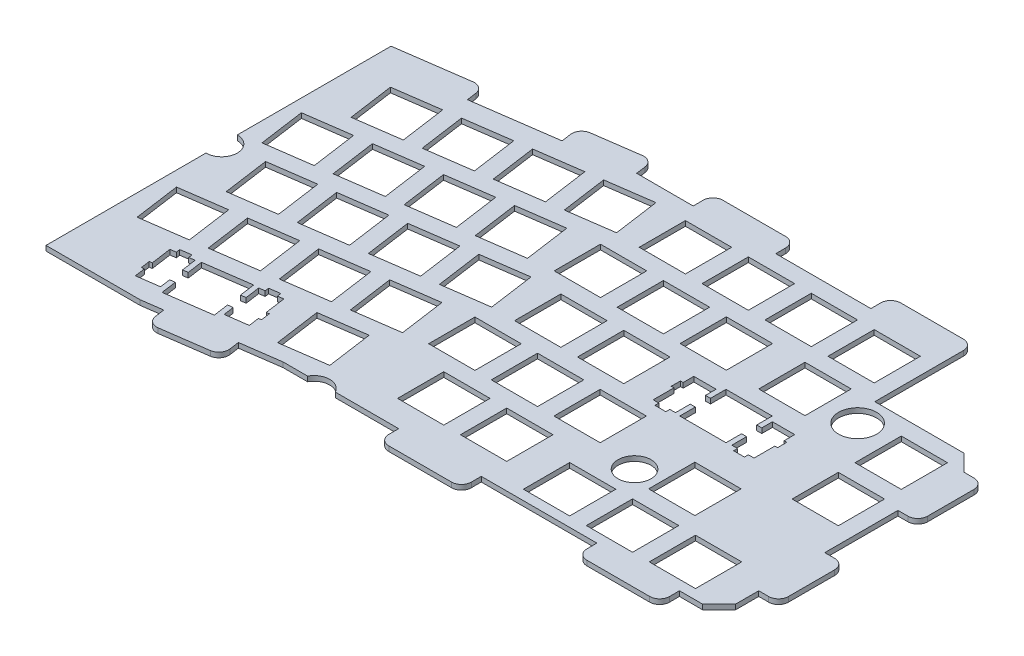
SolidWorks part; units mm, degrees
material "ABS PC"
ref_plane "Front Plane" through (0, 0, 0) normal (0, 0, 1) x (1, 0, 0)
ref_plane "Top Plane" through (0, 0, 0) normal (0, 1, 0) x (1, 0, 0)
ref_plane "Right Plane" through (0, 0, 0) normal (1, 0, 0) x (0, 0, -1)
sketch "Sketch1" plane through (0, 0, 0) normal (0, 1, 0) x (1, 0, 0)
  line L9 (219.1541, 94.4547) -> (218.9175, 96.1382)
  line L10 (165.0257, -13.8474) -> (202.9837, -8.5128)
  line L11 (136.5182, -13.8474) -> (165.0257, -13.8474)
  line L12 (136.5182, 84.5577) -> (136.5182, -13.8474)
  line L13 (218.9175, 96.1382) -> (136.5182, 84.5577)
  line L14 (219.1541, 94.4547) -> (218.9175, 96.1382)
  line L15 (302.957, 70.6408) -> (302.957, 94.4547)
  line L16 (334.9639, 70.6408) -> (302.957, 70.6408)
  line L17 (334.9639, -8.5128) -> (334.9639, 70.6408)
  line L19 (165.0257, -13.8474) -> (202.9837, -8.5128)
  line L20 (136.5182, -13.8474) -> (165.0257, -13.8474)
  line L21 (136.5182, 84.5577) -> (136.5182, -13.8474)
  line L22 (218.9175, 96.1382) -> (136.5182, 84.5577)
  line L24 (302.957, 70.6408) -> (302.957, 94.4547)
  line L25 (334.9639, 70.6408) -> (302.957, 70.6408)
  line L26 (334.9639, -8.5128) -> (334.9639, 70.6408)
  line L172 (302.957, 94.4547) -> (219.1541, 94.4547)
  line L173 (302.957, 94.4547) -> (219.1541, 94.4547)
  line L174 (202.9837, -8.5128) -> (334.9639, -8.5128)
  line L175 (202.9837, -8.5128) -> (334.9639, -8.5128)
  line L263 (136.5182, 95.7385) -> (136.5182, -17.0974) construction
  dimension "D1" = 0
extrude "Boss-Extrude1" add sketch "Sketch1" against normal blind 1.5
sketch "Sketch2" plane through (0, 0, 0) normal (0, 1, 0) x (1, 0, 0)
  line L4 (16.668, 52.1024) -> (2.668, 52.1024)
  line L5 (16.668, 38.1024) -> (16.668, 52.1024)
  line L6 (2.668, 38.1024) -> (16.668, 38.1024)
  line L7 (2.668, 52.1024) -> (2.668, 38.1024)
  line L8 (16.668, 52.1024) -> (2.668, 52.1024)
  line L9 (16.668, 38.1024) -> (16.668, 52.1024)
  line L10 (2.668, 38.1024) -> (16.668, 38.1024)
  line L11 (2.668, 52.1024) -> (2.668, 38.1024)
  line L12 (42.8632, 52.1024) -> (28.8632, 52.1024)
  line L13 (42.8632, 38.1024) -> (42.8632, 52.1024)
  line L14 (28.8632, 38.1024) -> (42.8632, 38.1024)
  line L15 (28.8632, 52.1024) -> (28.8632, 38.1024)
  line L16 (42.8632, 52.1024) -> (28.8632, 52.1024)
  line L17 (42.8632, 38.1024) -> (42.8632, 52.1024)
  line L18 (28.8632, 38.1024) -> (42.8632, 38.1024)
  line L19 (28.8632, 52.1024) -> (28.8632, 38.1024)
  line L20 (241.1855, 51.3524) -> (227.1855, 51.3524)
  line L21 (241.1855, 37.3524) -> (241.1855, 51.3524)
  line L22 (227.1855, 37.3524) -> (241.1855, 37.3524)
  line L23 (227.1855, 51.3524) -> (227.1855, 37.3524)
  line L24 (241.1855, 51.3524) -> (227.1855, 51.3524)
  line L25 (241.1855, 37.3524) -> (241.1855, 51.3524)
  line L26 (227.1855, 37.3524) -> (241.1855, 37.3524)
  line L27 (227.1855, 51.3524) -> (227.1855, 37.3524)
  line L28 (178.1211, 64.9018) -> (180.0695, 51.0381)
  line L29 (180.0695, 51.0381) -> (193.9333, 52.9865)
  line L30 (193.9333, 52.9865) -> (191.9848, 66.8503)
  line L31 (191.9848, 66.8503) -> (178.1211, 64.9018)
  line L32 (178.1211, 64.9018) -> (180.0695, 51.0381)
  line L33 (180.0695, 51.0381) -> (193.9333, 52.9865)
  line L34 (193.9333, 52.9865) -> (191.9848, 66.8503)
  line L35 (191.9848, 66.8503) -> (178.1211, 64.9018)
  line L36 (104.7514, 50.596) -> (118.6152, 48.6476)
  line L37 (118.6152, 48.6476) -> (120.5636, 62.5114)
  line L38 (120.5636, 62.5114) -> (106.6998, 64.4598)
  line L39 (106.6998, 64.4598) -> (104.7514, 50.596)
  line L40 (104.7514, 50.596) -> (118.6152, 48.6476)
  line L41 (118.6152, 48.6476) -> (120.5636, 62.5114)
  line L42 (120.5636, 62.5114) -> (106.6998, 64.4598)
  line L43 (106.6998, 64.4598) -> (104.7514, 50.596)
  line L44 (159.2557, 62.2517) -> (161.2042, 48.388)
  line L45 (161.2042, 48.388) -> (175.0679, 50.3364)
  line L46 (175.0679, 50.3364) -> (173.1195, 64.2001)
  line L47 (173.1195, 64.2001) -> (159.2557, 62.2517)
  line L48 (159.2557, 62.2517) -> (161.2042, 48.388)
  line L49 (161.2042, 48.388) -> (175.0679, 50.3364)
  line L50 (175.0679, 50.3364) -> (173.1195, 64.2001)
  line L51 (173.1195, 64.2001) -> (159.2557, 62.2517)
  line L52 (156.2021, 47.683) -> (154.2536, 61.5467)
  line L53 (154.2536, 61.5467) -> (140.3899, 59.5983)
  line L54 (140.3899, 59.5983) -> (142.3383, 45.7346)
  line L55 (142.3383, 45.7346) -> (156.2021, 47.683)
  line L56 (156.2021, 47.683) -> (154.2536, 61.5467)
  line L57 (154.2536, 61.5467) -> (140.3899, 59.5983)
  line L58 (140.3899, 59.5983) -> (142.3383, 45.7346)
  line L59 (142.3383, 45.7346) -> (156.2021, 47.683)
  line L60 (67.0198, 55.899) -> (80.8836, 53.9505)
  line L61 (80.8836, 53.9505) -> (82.832, 67.8143)
  line L62 (82.832, 67.8143) -> (68.9683, 69.7627)
  line L63 (68.9683, 69.7627) -> (67.0198, 55.899)
  line L64 (67.0198, 55.899) -> (80.8836, 53.9505)
  line L65 (80.8836, 53.9505) -> (82.832, 67.8143)
  line L66 (82.832, 67.8143) -> (68.9683, 69.7627)
  line L67 (68.9683, 69.7627) -> (67.0198, 55.899)
  line L68 (196.9864, 67.5526) -> (198.9348, 53.6888)
  line L69 (198.9348, 53.6888) -> (212.7985, 55.6372)
  line L70 (212.7985, 55.6372) -> (210.8501, 69.501)
  line L71 (210.8501, 69.501) -> (196.9864, 67.5526)
  line L72 (196.9864, 67.5526) -> (198.9348, 53.6888)
  line L73 (198.9348, 53.6888) -> (212.7985, 55.6372)
  line L74 (212.7985, 55.6372) -> (210.8501, 69.501)
  line L75 (210.8501, 69.501) -> (196.9864, 67.5526)
  line L76 (329.9639, 65.6408) -> (315.9639, 65.6408)
  line L77 (329.9639, 51.6408) -> (329.9639, 65.6408)
  line L78 (315.9639, 51.6408) -> (329.9639, 51.6408)
  line L79 (315.9639, 65.6408) -> (315.9639, 51.6408)
  line L80 (329.9639, 65.6408) -> (315.9639, 65.6408)
  line L81 (329.9639, 51.6408) -> (329.9639, 65.6408)
  line L82 (315.9639, 51.6408) -> (329.9639, 51.6408)
  line L83 (315.9639, 65.6408) -> (315.9639, 51.6408)
  line L84 (101.698, 65.1623) -> (87.8343, 67.1107)
  line L85 (87.8343, 67.1107) -> (85.8859, 53.247)
  line L86 (85.8859, 53.247) -> (99.7496, 51.2985)
  line L87 (99.7496, 51.2985) -> (101.698, 65.1623)
  line L88 (101.698, 65.1623) -> (87.8343, 67.1107)
  line L89 (87.8343, 67.1107) -> (85.8859, 53.247)
  line L90 (85.8859, 53.247) -> (99.7496, 51.2985)
  line L91 (99.7496, 51.2985) -> (101.698, 65.1623)
  line L92 (253.1873, 70.4036) -> (239.1873, 70.4036)
  line L93 (253.1873, 56.4036) -> (253.1873, 70.4036)
  line L94 (239.1873, 56.4036) -> (253.1873, 56.4036)
  line L95 (239.1873, 70.4036) -> (239.1873, 56.4036)
  line L96 (253.1873, 70.4036) -> (239.1873, 70.4036)
  line L97 (253.1873, 56.4036) -> (253.1873, 70.4036)
  line L98 (239.1873, 56.4036) -> (253.1873, 56.4036)
  line L99 (239.1873, 70.4036) -> (239.1873, 56.4036)
  line L100 (272.2384, 70.4036) -> (258.2384, 70.4036)
  line L101 (272.2384, 56.4036) -> (272.2384, 70.4036)
  line L102 (258.2384, 56.4036) -> (272.2384, 56.4036)
  line L103 (258.2384, 70.4036) -> (258.2384, 56.4036)
  line L104 (272.2384, 70.4036) -> (258.2384, 70.4036)
  line L105 (272.2384, 56.4036) -> (272.2384, 70.4036)
  line L106 (258.2384, 56.4036) -> (272.2384, 56.4036)
  line L107 (258.2384, 70.4036) -> (258.2384, 56.4036)
  line L108 (296.0529, 70.4036) -> (282.0529, 70.4036)
  line L109 (296.0529, 56.4036) -> (296.0529, 70.4036)
  line L110 (282.0529, 56.4036) -> (296.0529, 56.4036)
  line L111 (282.0529, 70.4036) -> (282.0529, 56.4036)
  line L112 (296.0529, 70.4036) -> (282.0529, 70.4036)
  line L113 (296.0529, 56.4036) -> (296.0529, 70.4036)
  line L114 (282.0529, 56.4036) -> (296.0529, 56.4036)
  line L115 (282.0529, 70.4036) -> (282.0529, 56.4036)
  line L116 (63.9638, 70.468) -> (50.1, 72.4164)
  line L117 (50.1, 72.4164) -> (48.1516, 58.5526)
  line L118 (48.1516, 58.5526) -> (62.0153, 56.6042)
  line L119 (62.0153, 56.6042) -> (63.9638, 70.468)
  line L120 (63.9638, 70.468) -> (50.1, 72.4164)
  line L121 (50.1, 72.4164) -> (48.1516, 58.5526)
  line L122 (48.1516, 58.5526) -> (62.0153, 56.6042)
  line L123 (62.0153, 56.6042) -> (63.9638, 70.468)
  line L124 (157.57, -5.1025) -> (158.0197, -8.301)
  line L125 (158.0197, -8.301) -> (164.7049, -7.3597)
  line L126 (164.7049, -7.3597) -> (164.2552, -4.1612)
  line L127 (164.2552, -4.1612) -> (165.7652, -3.9487)
  line L128 (165.7652, -3.9487) -> (166.4193, -8.6024)
  line L129 (166.4193, -8.6024) -> (180.283, -6.654)
  line L130 (180.283, -6.654) -> (179.6288, -1.9986)
  line L131 (179.6288, -1.9986) -> (181.1399, -1.7869)
  line L132 (181.1399, -1.7869) -> (181.5889, -4.9856)
  line L133 (181.5889, -4.9856) -> (188.2726, -4.0495)
  line L134 (188.2726, -4.0495) -> (187.8237, -0.8493)
  line L135 (187.8237, -0.8493) -> (188.6407, -0.7352)
  line L136 (188.6407, -0.7352) -> (188.2539, 2.0361)
  line L137 (188.2539, 2.0361) -> (187.4358, 1.922)
  line L138 (187.4358, 1.922) -> (186.5659, 8.1321)
  line L139 (186.5659, 8.1321) -> (184.8567, 7.8916)
  line L140 (184.8567, 7.8916) -> (184.6901, 9.0809)
  line L141 (184.6901, 9.0809) -> (181.4217, 8.6218)
  line L142 (181.4217, 8.6218) -> (181.5893, 7.4338)
  line L143 (181.5893, 7.4338) -> (179.8801, 7.1932)
  line L144 (179.8801, 7.1932) -> (180.5017, 2.7678)
  line L145 (180.5017, 2.7678) -> (178.9915, 2.5561)
  line L146 (178.9915, 2.5561) -> (178.338, 7.2102)
  line L147 (178.338, 7.2102) -> (164.4743, 5.2618)
  line L148 (164.4743, 5.2618) -> (165.1265, 0.6064)
  line L149 (165.1265, 0.6064) -> (163.6163, 0.3958)
  line L150 (163.6163, 0.3958) -> (162.9951, 4.8211)
  line L151 (162.9951, 4.8211) -> (161.287, 4.5816)
  line L152 (161.287, 4.5816) -> (161.1202, 5.771)
  line L153 (161.1202, 5.771) -> (157.8529, 5.3113)
  line L154 (157.8529, 5.3113) -> (158.0197, 4.1233)
  line L155 (158.0197, 4.1233) -> (156.3089, 3.8836)
  line L156 (156.3089, 3.8836) -> (157.1794, -2.3298)
  line L157 (157.1794, -2.3298) -> (156.3634, -2.4444)
  line L158 (156.3634, -2.4444) -> (156.754, -5.2171)
  line L159 (156.754, -5.2171) -> (157.57, -5.1025)
  line L160 (157.57, -5.1025) -> (158.0197, -8.301)
  line L161 (158.0197, -8.301) -> (164.7049, -7.3597)
  line L162 (164.7049, -7.3597) -> (164.2552, -4.1612)
  line L163 (164.2552, -4.1612) -> (165.7652, -3.9487)
  line L164 (165.7652, -3.9487) -> (166.4193, -8.6024)
  line L165 (166.4193, -8.6024) -> (180.283, -6.654)
  line L166 (180.283, -6.654) -> (179.6288, -1.9986)
  line L167 (179.6288, -1.9986) -> (181.1399, -1.7869)
  line L168 (181.1399, -1.7869) -> (181.5889, -4.9856)
  line L169 (181.5889, -4.9856) -> (188.2726, -4.0495)
  line L170 (188.2726, -4.0495) -> (187.8237, -0.8493)
  line L171 (187.8237, -0.8493) -> (188.6407, -0.7352)
  line L172 (188.6407, -0.7352) -> (188.2539, 2.0361)
  line L173 (188.2539, 2.0361) -> (187.4358, 1.922)
  line L174 (187.4358, 1.922) -> (186.5659, 8.1321)
  line L175 (186.5659, 8.1321) -> (184.8567, 7.8916)
  line L176 (184.8567, 7.8916) -> (184.6901, 9.0809)
  line L177 (184.6901, 9.0809) -> (181.4217, 8.6218)
  line L178 (181.4217, 8.6218) -> (181.5893, 7.4338)
  line L179 (181.5893, 7.4338) -> (179.8801, 7.1932)
  line L180 (179.8801, 7.1932) -> (180.5017, 2.7678)
  line L181 (180.5017, 2.7678) -> (178.9915, 2.5561)
  line L182 (178.9915, 2.5561) -> (178.338, 7.2102)
  line L183 (178.338, 7.2102) -> (164.4743, 5.2618)
  line L184 (164.4743, 5.2618) -> (165.1265, 0.6064)
  line L185 (165.1265, 0.6064) -> (163.6163, 0.3958)
  line L186 (163.6163, 0.3958) -> (162.9951, 4.8211)
  line L187 (162.9951, 4.8211) -> (161.287, 4.5816)
  line L188 (161.287, 4.5816) -> (161.1202, 5.771)
  line L189 (161.1202, 5.771) -> (157.8529, 5.3113)
  line L190 (157.8529, 5.3113) -> (158.0197, 4.1233)
  line L191 (158.0197, 4.1233) -> (156.3089, 3.8836)
  line L192 (156.3089, 3.8836) -> (157.1794, -2.3298)
  line L193 (157.1794, -2.3298) -> (156.3634, -2.4444)
  line L194 (156.3634, -2.4444) -> (156.754, -5.2171)
  line L195 (156.754, -5.2171) -> (157.57, -5.1025)
  line L196 (147.1695, 79.7839) -> (149.118, 65.9202)
  line L197 (149.118, 65.9202) -> (162.9817, 67.8686)
  line L198 (162.9817, 67.8686) -> (161.0333, 81.7324)
  line L199 (161.0333, 81.7324) -> (147.1695, 79.7839)
  line L200 (147.1695, 79.7839) -> (149.118, 65.9202)
  line L201 (149.118, 65.9202) -> (162.9817, 67.8686)
  line L202 (162.9817, 67.8686) -> (161.0333, 81.7324)
  line L203 (161.0333, 81.7324) -> (147.1695, 79.7839)
  line L204 (16.9533, 71.1536) -> (2.9533, 71.1536)
  line L205 (16.9533, 57.1536) -> (16.9533, 71.1536)
  line L206 (2.9533, 57.1536) -> (16.9533, 57.1536)
  line L207 (2.9533, 71.1536) -> (2.9533, 57.1536)
  line L208 (16.9533, 71.1536) -> (2.9533, 71.1536)
  line L209 (16.9533, 57.1536) -> (16.9533, 71.1536)
  line L210 (2.9533, 57.1536) -> (16.9533, 57.1536)
  line L211 (2.9533, 71.1536) -> (2.9533, 57.1536)
  line L212 (40.7687, 71.1536) -> (26.7687, 71.1536)
  line L213 (40.7687, 57.1536) -> (40.7687, 71.1536)
  line L214 (26.7687, 57.1536) -> (40.7687, 57.1536)
  line L215 (26.7687, 71.1536) -> (26.7687, 57.1536)
  line L216 (40.7687, 71.1536) -> (26.7687, 71.1536)
  line L217 (40.7687, 57.1536) -> (40.7687, 71.1536)
  line L218 (26.7687, 57.1536) -> (40.7687, 57.1536)
  line L219 (26.7687, 71.1536) -> (26.7687, 57.1536)
  line L220 (220.1361, 56.4036) -> (234.1361, 56.4036)
  line L221 (220.1361, 70.4036) -> (220.1361, 56.4036)
  line L222 (234.1361, 70.4036) -> (220.1361, 70.4036)
  line L223 (234.1361, 56.4036) -> (234.1361, 70.4036)
  line L224 (220.1361, 56.4036) -> (234.1361, 56.4036)
  line L225 (220.1361, 70.4036) -> (220.1361, 56.4036)
  line L226 (234.1361, 70.4036) -> (220.1361, 70.4036)
  line L227 (234.1361, 56.4036) -> (234.1361, 70.4036)
  line L228 (324.8196, 8.4872) -> (310.8196, 8.4872)
  line L229 (324.8196, -5.5128) -> (324.8196, 8.4872)
  line L230 (310.8196, -5.5128) -> (324.8196, -5.5128)
  line L231 (310.8196, 8.4872) -> (310.8196, -5.5128)
  line L232 (324.8196, 8.4872) -> (310.8196, 8.4872)
  line L233 (324.8196, -5.5128) -> (324.8196, 8.4872)
  line L234 (310.8196, -5.5128) -> (324.8196, -5.5128)
  line L235 (310.8196, 8.4872) -> (310.8196, -5.5128)
  line L236 (184.9019, 85.0909) -> (186.8504, 71.2271)
  line L237 (186.8504, 71.2271) -> (200.7141, 73.1755)
  line L238 (200.7141, 73.1755) -> (198.7657, 87.0393)
  line L239 (198.7657, 87.0393) -> (184.9019, 85.0909)
  line L240 (184.9019, 85.0909) -> (186.8504, 71.2271)
  line L241 (186.8504, 71.2271) -> (200.7141, 73.1755)
  line L242 (200.7141, 73.1755) -> (198.7657, 87.0393)
  line L243 (198.7657, 87.0393) -> (184.9019, 85.0909)
  line L244 (97.9699, 70.7881) -> (111.8336, 68.8397)
  line L245 (111.8336, 68.8397) -> (113.7821, 82.7035)
  line L246 (113.7821, 82.7035) -> (99.9183, 84.6519)
  line L247 (99.9183, 84.6519) -> (97.9699, 70.7881)
  line L248 (97.9699, 70.7881) -> (111.8336, 68.8397)
  line L249 (111.8336, 68.8397) -> (113.7821, 82.7035)
  line L250 (113.7821, 82.7035) -> (99.9183, 84.6519)
  line L251 (99.9183, 84.6519) -> (97.9699, 70.7881)
  line L252 (166.0364, 82.4413) -> (167.9848, 68.5776)
  line L253 (167.9848, 68.5776) -> (181.8485, 70.526)
  line L254 (181.8485, 70.526) -> (179.9001, 84.3897)
  line L255 (179.9001, 84.3897) -> (166.0364, 82.4413)
  line L256 (166.0364, 82.4413) -> (167.9848, 68.5776)
  line L257 (167.9848, 68.5776) -> (181.8485, 70.526)
  line L258 (181.8485, 70.526) -> (179.9001, 84.3897)
  line L259 (179.9001, 84.3897) -> (166.0364, 82.4413)
  line L260 (132.6465, 80.0523) -> (118.7828, 82.0008)
  line L261 (118.7828, 82.0008) -> (116.8343, 68.137)
  line L262 (116.8343, 68.137) -> (130.6981, 66.1886)
  line L263 (130.6981, 66.1886) -> (132.6465, 80.0523)
  line L264 (132.6465, 80.0523) -> (118.7828, 82.0008)
  line L265 (118.7828, 82.0008) -> (116.8343, 68.137)
  line L266 (116.8343, 68.137) -> (130.6981, 66.1886)
  line L267 (130.6981, 66.1886) -> (132.6465, 80.0523)
  line L268 (111.1042, 1.3782) -> (109.5931, 1.5905)
  line L269 (109.5931, 1.5905) -> (110.2481, 6.2457)
  line L270 (110.2481, 6.2457) -> (96.3844, 8.1942)
  line L271 (96.3844, 8.1942) -> (95.7296, 3.5418)
  line L272 (95.7296, 3.5418) -> (94.2205, 3.7527)
  line L273 (94.2205, 3.7527) -> (94.8425, 8.1806)
  line L274 (94.8425, 8.1806) -> (93.1334, 8.4204)
  line L275 (93.1334, 8.4204) -> (93.3014, 9.6083)
  line L276 (93.3014, 9.6083) -> (90.0324, 10.0671)
  line L277 (90.0324, 10.0671) -> (89.8659, 8.8792)
  line L278 (89.8659, 8.8792) -> (88.1583, 9.1189)
  line L279 (88.1583, 9.1189) -> (87.2845, 2.9106)
  line L280 (87.2845, 2.9106) -> (86.4675, 3.0249)
  line L281 (86.4675, 3.0249) -> (86.0773, 0.2521)
  line L282 (86.0773, 0.2521) -> (86.8948, 0.1364)
  line L283 (86.8948, 0.1364) -> (86.4453, -3.0609)
  line L284 (86.4453, -3.0609) -> (93.1306, -4.0007)
  line L285 (93.1306, -4.0007) -> (93.5796, -0.8021)
  line L286 (93.5796, -0.8021) -> (95.0907, -1.0143)
  line L287 (95.0907, -1.0143) -> (94.4357, -5.6696)
  line L288 (94.4357, -5.6696) -> (108.2995, -7.618)
  line L289 (108.2995, -7.618) -> (108.9549, -2.9641)
  line L290 (108.9549, -2.9641) -> (110.465, -3.1765)
  line L291 (110.465, -3.1765) -> (110.0157, -6.3751)
  line L292 (110.0157, -6.3751) -> (116.699, -7.3155)
  line L293 (116.699, -7.3155) -> (117.1503, -4.1155)
  line L294 (117.1503, -4.1155) -> (117.9673, -4.2313)
  line L295 (117.9673, -4.2313) -> (118.3576, -1.4586)
  line L296 (118.3576, -1.4586) -> (117.5405, -1.3441)
  line L297 (117.5405, -1.3441) -> (118.4121, 4.8656)
  line L298 (118.4121, 4.8656) -> (116.7015, 5.1061)
  line L299 (116.7015, 5.1061) -> (116.8685, 6.2954)
  line L300 (116.8685, 6.2954) -> (113.6013, 6.7543)
  line L301 (113.6013, 6.7543) -> (113.4343, 5.5663)
  line L302 (113.4343, 5.5663) -> (111.7252, 5.8061)
  line L303 (111.7252, 5.8061) -> (111.1042, 1.3782)
  line L304 (111.1042, 1.3782) -> (109.5931, 1.5905)
  line L305 (109.5931, 1.5905) -> (110.2481, 6.2457)
  line L306 (110.2481, 6.2457) -> (96.3844, 8.1942)
  line L307 (96.3844, 8.1942) -> (95.7296, 3.5418)
  line L308 (95.7296, 3.5418) -> (94.2205, 3.7527)
  line L309 (94.2205, 3.7527) -> (94.8425, 8.1806)
  line L310 (94.8425, 8.1806) -> (93.1334, 8.4204)
  line L311 (93.1334, 8.4204) -> (93.3014, 9.6083)
  line L312 (93.3014, 9.6083) -> (90.0324, 10.0671)
  line L313 (90.0324, 10.0671) -> (89.8659, 8.8792)
  line L314 (89.8659, 8.8792) -> (88.1583, 9.1189)
  line L315 (88.1583, 9.1189) -> (87.2845, 2.9106)
  line L316 (87.2845, 2.9106) -> (86.4675, 3.0249)
  line L317 (86.4675, 3.0249) -> (86.0773, 0.2521)
  line L318 (86.0773, 0.2521) -> (86.8948, 0.1364)
  line L319 (86.8948, 0.1364) -> (86.4453, -3.0609)
  line L320 (86.4453, -3.0609) -> (93.1306, -4.0007)
  line L321 (93.1306, -4.0007) -> (93.5796, -0.8021)
  line L322 (93.5796, -0.8021) -> (95.0907, -1.0143)
  line L323 (95.0907, -1.0143) -> (94.4357, -5.6696)
  line L324 (94.4357, -5.6696) -> (108.2995, -7.618)
  line L325 (108.2995, -7.618) -> (108.9549, -2.9641)
  line L326 (108.9549, -2.9641) -> (110.465, -3.1765)
  line L327 (110.465, -3.1765) -> (110.0157, -6.3751)
  line L328 (110.0157, -6.3751) -> (116.699, -7.3155)
  line L329 (116.699, -7.3155) -> (117.1503, -4.1155)
  line L330 (117.1503, -4.1155) -> (117.9673, -4.2313)
  line L331 (117.9673, -4.2313) -> (118.3576, -1.4586)
  line L332 (118.3576, -1.4586) -> (117.5405, -1.3441)
  line L333 (117.5405, -1.3441) -> (118.4121, 4.8656)
  line L334 (118.4121, 4.8656) -> (116.7015, 5.1061)
  line L335 (116.7015, 5.1061) -> (116.8685, 6.2954)
  line L336 (116.8685, 6.2954) -> (113.6013, 6.7543)
  line L337 (113.6013, 6.7543) -> (113.4343, 5.5663)
  line L338 (113.4343, 5.5663) -> (111.7252, 5.8061)
  line L339 (111.7252, 5.8061) -> (111.1042, 1.3782)
  line L340 (56.7058, -0.3668) -> (70.5695, -2.3152)
  line L341 (70.5695, -2.3152) -> (72.518, 11.5486)
  line L342 (72.518, 11.5486) -> (58.6542, 13.497)
  line L343 (58.6542, 13.497) -> (56.7058, -0.3668)
  line L344 (56.7058, -0.3668) -> (70.5695, -2.3152)
  line L345 (70.5695, -2.3152) -> (72.518, 11.5486)
  line L346 (72.518, 11.5486) -> (58.6542, 13.497)
  line L347 (58.6542, 13.497) -> (56.7058, -0.3668)
  line L348 (195.1301, 9.5671) -> (197.0785, -4.2966)
  line L349 (197.0785, -4.2966) -> (210.9422, -2.3482)
  line L350 (210.9422, -2.3482) -> (208.9938, 11.5155)
  line L351 (208.9938, 11.5155) -> (195.1301, 9.5671)
  line L352 (195.1301, 9.5671) -> (197.0785, -4.2966)
  line L353 (197.0785, -4.2966) -> (210.9422, -2.3482)
  line L354 (210.9422, -2.3482) -> (208.9938, 11.5155)
  line L355 (208.9938, 11.5155) -> (195.1301, 9.5671)
  line L356 (286.7173, 8.4872) -> (272.7173, 8.4872)
  line L357 (286.7173, -5.5128) -> (286.7173, 8.4872)
  line L358 (272.7173, -5.5128) -> (286.7173, -5.5128)
  line L359 (272.7173, 8.4872) -> (272.7173, -5.5128)
  line L360 (286.7173, 8.4872) -> (272.7173, 8.4872)
  line L361 (286.7173, -5.5128) -> (286.7173, 8.4872)
  line L362 (272.7173, -5.5128) -> (286.7173, -5.5128)
  line L363 (272.7173, 8.4872) -> (272.7173, -5.5128)
  line L364 (291.7685, -5.5128) -> (305.7685, -5.5128)
  line L365 (291.7685, 8.4872) -> (291.7685, -5.5128)
  line L366 (305.7685, 8.4872) -> (291.7685, 8.4872)
  line L367 (305.7685, -5.5128) -> (305.7685, 8.4872)
  line L368 (291.7685, -5.5128) -> (305.7685, -5.5128)
  line L369 (291.7685, 8.4872) -> (291.7685, -5.5128)
  line L370 (305.7685, 8.4872) -> (291.7685, 8.4872)
  line L371 (305.7685, -5.5128) -> (305.7685, 8.4872)
  line L372 (329.9639, 89.4547) -> (315.9639, 89.4547)
  line L373 (329.9639, 75.4547) -> (329.9639, 89.4547)
  line L374 (315.9639, 75.4547) -> (329.9639, 75.4547)
  line L375 (315.9639, 89.4547) -> (315.9639, 75.4547)
  line L376 (329.9639, 89.4547) -> (315.9639, 89.4547)
  line L377 (329.9639, 75.4547) -> (329.9639, 89.4547)
  line L378 (315.9639, 75.4547) -> (329.9639, 75.4547)
  line L379 (315.9639, 89.4547) -> (315.9639, 75.4547)
  line L380 (60.2383, 76.0914) -> (74.102, 74.143)
  line L381 (74.102, 74.143) -> (76.0505, 88.0067)
  line L382 (76.0505, 88.0067) -> (62.1867, 89.9552)
  line L383 (62.1867, 89.9552) -> (60.2383, 76.0914)
  line L384 (60.2383, 76.0914) -> (74.102, 74.143)
  line L385 (74.102, 74.143) -> (76.0505, 88.0067)
  line L386 (76.0505, 88.0067) -> (62.1867, 89.9552)
  line L387 (62.1867, 89.9552) -> (60.2383, 76.0914)
  line L388 (203.7677, 87.7438) -> (205.7162, 73.88)
  line L389 (205.7162, 73.88) -> (219.5799, 75.8285)
  line L390 (219.5799, 75.8285) -> (217.6315, 89.6922)
  line L391 (217.6315, 89.6922) -> (203.7677, 87.7438)
  line L392 (203.7677, 87.7438) -> (205.7162, 73.88)
  line L393 (205.7162, 73.88) -> (219.5799, 75.8285)
  line L394 (219.5799, 75.8285) -> (217.6315, 89.6922)
  line L395 (217.6315, 89.6922) -> (203.7677, 87.7438)
  line L396 (94.9166, 85.3549) -> (81.0528, 87.3033)
  line L397 (81.0528, 87.3033) -> (79.1044, 73.4396)
  line L398 (79.1044, 73.4396) -> (92.9682, 71.4911)
  line L399 (92.9682, 71.4911) -> (94.9166, 85.3549)
  line L400 (94.9166, 85.3549) -> (81.0528, 87.3033)
  line L401 (81.0528, 87.3033) -> (79.1044, 73.4396)
  line L402 (79.1044, 73.4396) -> (92.9682, 71.4911)
  line L403 (92.9682, 71.4911) -> (94.9166, 85.3549)
  line L404 (13.9985, 14.0032) -> (-0.0015, 14.0032)
  line L405 (13.9985, 0.0032) -> (13.9985, 14.0032)
  line L406 (-0.0015, 0.0032) -> (13.9985, 0.0032)
  line L407 (-0.0015, 14.0032) -> (-0.0015, 0.0032)
  line L408 (13.9985, 14.0032) -> (-0.0015, 14.0032)
  line L409 (13.9985, 0.0032) -> (13.9985, 14.0032)
  line L410 (-0.0015, 0.0032) -> (13.9985, 0.0032)
  line L411 (-0.0015, 14.0032) -> (-0.0015, 0.0032)
  line L412 (37.8153, 14) -> (23.8153, 14)
  line L413 (37.8153, 0) -> (37.8153, 14)
  line L414 (23.8153, 0) -> (37.8153, 0)
  line L415 (23.8153, 14) -> (23.8153, 0)
  line L416 (37.8153, 14) -> (23.8153, 14)
  line L417 (37.8153, 0) -> (37.8153, 14)
  line L418 (23.8153, 0) -> (37.8153, 0)
  line L419 (23.8153, 14) -> (23.8153, 0)
  line L420 (243.8527, 13.25) -> (229.8527, 13.25)
  line L421 (243.8527, -0.75) -> (243.8527, 13.25)
  line L422 (229.8527, -0.75) -> (243.8527, -0.75)
  line L423 (229.8527, 13.25) -> (229.8527, -0.75)
  line L424 (243.8527, 13.25) -> (229.8527, 13.25)
  line L425 (243.8527, -0.75) -> (243.8527, 13.25)
  line L426 (229.8527, -0.75) -> (243.8527, -0.75)
  line L427 (229.8527, 13.25) -> (229.8527, -0.75)
  line L428 (248.9019, -0.75) -> (262.9019, -0.75)
  line L429 (248.9019, 13.25) -> (248.9019, -0.75)
  line L430 (262.9019, 13.25) -> (248.9019, 13.25)
  line L431 (262.9019, -0.75) -> (262.9019, 13.25)
  line L432 (248.9019, -0.75) -> (262.9019, -0.75)
  line L433 (248.9019, 13.25) -> (248.9019, -0.75)
  line L434 (262.9019, 13.25) -> (248.9019, 13.25)
  line L435 (262.9019, -0.75) -> (262.9019, 13.25)
  line L436 (240.8054, 89.4547) -> (226.8054, 89.4547)
  line L437 (240.8054, 75.4547) -> (240.8054, 89.4547)
  line L438 (226.8054, 75.4547) -> (240.8054, 75.4547)
  line L439 (226.8054, 89.4547) -> (226.8054, 75.4547)
  line L440 (240.8054, 89.4547) -> (226.8054, 89.4547)
  line L441 (240.8054, 75.4547) -> (240.8054, 89.4547)
  line L442 (226.8054, 75.4547) -> (240.8054, 75.4547)
  line L443 (226.8054, 89.4547) -> (226.8054, 75.4547)
  line L444 (259.8537, 89.4547) -> (245.8537, 89.4547)
  line L445 (259.8537, 75.4547) -> (259.8537, 89.4547)
  line L446 (245.8537, 75.4547) -> (259.8537, 75.4547)
  line L447 (245.8537, 89.4547) -> (245.8537, 75.4547)
  line L448 (259.8537, 89.4547) -> (245.8537, 89.4547)
  line L449 (259.8537, 75.4547) -> (259.8537, 89.4547)
  line L450 (245.8537, 75.4547) -> (259.8537, 75.4547)
  line L451 (245.8537, 89.4547) -> (245.8537, 75.4547)
  line L452 (278.9058, 89.4547) -> (264.9058, 89.4547)
  line L453 (278.9058, 75.4547) -> (278.9058, 89.4547)
  line L454 (264.9058, 75.4547) -> (278.9058, 75.4547)
  line L455 (264.9058, 89.4547) -> (264.9058, 75.4547)
  line L456 (278.9058, 89.4547) -> (264.9058, 89.4547)
  line L457 (278.9058, 75.4547) -> (278.9058, 89.4547)
  line L458 (264.9058, 75.4547) -> (278.9058, 75.4547)
  line L459 (264.9058, 89.4547) -> (264.9058, 75.4547)
  line L460 (283.957, 75.4547) -> (297.957, 75.4547)
  line L461 (283.957, 89.4547) -> (283.957, 75.4547)
  line L462 (297.957, 89.4547) -> (283.957, 89.4547)
  line L463 (297.957, 75.4547) -> (297.957, 89.4547)
  line L464 (283.957, 75.4547) -> (297.957, 75.4547)
  line L465 (283.957, 89.4547) -> (283.957, 75.4547)
  line L466 (297.957, 89.4547) -> (283.957, 89.4547)
  line L467 (297.957, 75.4547) -> (297.957, 89.4547)
  line L468 (94.7285, 13.5308) -> (108.5923, 11.5823)
  line L469 (108.5923, 11.5823) -> (110.5407, 25.4461)
  line L470 (110.5407, 25.4461) -> (96.6769, 27.3945)
  line L471 (96.6769, 27.3945) -> (94.7285, 13.5308)
  line L472 (94.7285, 13.5308) -> (108.5923, 11.5823)
  line L473 (108.5923, 11.5823) -> (110.5407, 25.4461)
  line L474 (110.5407, 25.4461) -> (96.6769, 27.3945)
  line L475 (96.6769, 27.3945) -> (94.7285, 13.5308)
  line L476 (159.8401, 23.8549) -> (161.7885, 9.9912)
  line L477 (161.7885, 9.9912) -> (175.6523, 11.9396)
  line L478 (175.6523, 11.9396) -> (173.7039, 25.8034)
  line L479 (173.7039, 25.8034) -> (159.8401, 23.8549)
  line L480 (159.8401, 23.8549) -> (161.7885, 9.9912)
  line L481 (161.7885, 9.9912) -> (175.6523, 11.9396)
  line L482 (175.6523, 11.9396) -> (173.7039, 25.8034)
  line L483 (173.7039, 25.8034) -> (159.8401, 23.8549)
  line L484 (113.5965, 10.8786) -> (127.4602, 8.9301)
  line L485 (127.4602, 8.9301) -> (129.4086, 22.7939)
  line L486 (129.4086, 22.7939) -> (115.5449, 24.7423)
  line L487 (115.5449, 24.7423) -> (113.5965, 10.8786)
  line L488 (113.5965, 10.8786) -> (127.4602, 8.9301)
  line L489 (127.4602, 8.9301) -> (129.4086, 22.7939)
  line L490 (129.4086, 22.7939) -> (115.5449, 24.7423)
  line L491 (115.5449, 24.7423) -> (113.5965, 10.8786)
  line L492 (156.7871, 9.2881) -> (154.8387, 23.1518)
  line L493 (154.8387, 23.1518) -> (140.975, 21.2034)
  line L494 (140.975, 21.2034) -> (142.9234, 7.3397)
  line L495 (142.9234, 7.3397) -> (156.7871, 9.2881)
  line L496 (156.7871, 9.2881) -> (154.8387, 23.1518)
  line L497 (154.8387, 23.1518) -> (140.975, 21.2034)
  line L498 (140.975, 21.2034) -> (142.9234, 7.3397)
  line L499 (142.9234, 7.3397) -> (156.7871, 9.2881)
  line L500 (41.37, 78.7439) -> (55.2337, 76.7955)
  line L501 (55.2337, 76.7955) -> (57.1821, 90.6593)
  line L502 (57.1821, 90.6593) -> (43.3184, 92.6077)
  line L503 (43.3184, 92.6077) -> (41.37, 78.7439)
  line L504 (41.37, 78.7439) -> (55.2337, 76.7955)
  line L505 (55.2337, 76.7955) -> (57.1821, 90.6593)
  line L506 (57.1821, 90.6593) -> (43.3184, 92.6077)
  line L507 (43.3184, 92.6077) -> (41.37, 78.7439)
  line L508 (14.667, 90.2051) -> (0.667, 90.2051)
  line L509 (14.667, 76.2051) -> (14.667, 90.2051)
  line L510 (0.667, 76.2051) -> (14.667, 76.2051)
  line L511 (0.667, 90.2051) -> (0.667, 76.2051)
  line L512 (14.667, 90.2051) -> (0.667, 90.2051)
  line L513 (14.667, 76.2051) -> (14.667, 90.2051)
  line L514 (0.667, 76.2051) -> (14.667, 76.2051)
  line L515 (0.667, 90.2051) -> (0.667, 76.2051)
  line L516 (19.7182, 76.2047) -> (33.7182, 76.2047)
  line L517 (19.7182, 90.2047) -> (19.7182, 76.2047)
  line L518 (33.7182, 90.2047) -> (19.7182, 90.2047)
  line L519 (33.7182, 76.2047) -> (33.7182, 90.2047)
  line L520 (19.7182, 76.2047) -> (33.7182, 76.2047)
  line L521 (19.7182, 90.2047) -> (19.7182, 76.2047)
  line L522 (33.7182, 90.2047) -> (19.7182, 90.2047)
  line L523 (33.7182, 76.2047) -> (33.7182, 90.2047)
  line L524 (197.5716, 29.1561) -> (199.5201, 15.2924)
  line L525 (199.5201, 15.2924) -> (213.3838, 17.2408)
  line L526 (213.3838, 17.2408) -> (211.4354, 31.1046)
  line L527 (211.4354, 31.1046) -> (197.5716, 29.1561)
  line L528 (197.5716, 29.1561) -> (199.5201, 15.2924)
  line L529 (199.5201, 15.2924) -> (213.3838, 17.2408)
  line L530 (213.3838, 17.2408) -> (211.4354, 31.1046)
  line L531 (211.4354, 31.1046) -> (197.5716, 29.1561)
  line L532 (305.5785, 27.5384) -> (291.5785, 27.5384)
  line L533 (305.5785, 13.5384) -> (305.5785, 27.5384)
  line L534 (291.5785, 13.5384) -> (305.5785, 13.5384)
  line L535 (291.5785, 27.5384) -> (291.5785, 13.5384)
  line L536 (305.5785, 27.5384) -> (291.5785, 27.5384)
  line L537 (305.5785, 13.5384) -> (305.5785, 27.5384)
  line L538 (291.5785, 13.5384) -> (305.5785, 13.5384)
  line L539 (291.5785, 27.5384) -> (291.5785, 13.5384)
  line L540 (75.865, 16.1803) -> (89.7287, 14.2318)
  line L541 (89.7287, 14.2318) -> (91.6772, 28.0956)
  line L542 (91.6772, 28.0956) -> (77.8134, 30.044)
  line L543 (77.8134, 30.044) -> (75.865, 16.1803)
  line L544 (75.865, 16.1803) -> (89.7287, 14.2318)
  line L545 (89.7287, 14.2318) -> (91.6772, 28.0956)
  line L546 (91.6772, 28.0956) -> (77.8134, 30.044)
  line L547 (77.8134, 30.044) -> (75.865, 16.1803)
  line L548 (194.5187, 14.5909) -> (192.5702, 28.4546)
  line L549 (192.5702, 28.4546) -> (178.7065, 26.5062)
  line L550 (178.7065, 26.5062) -> (180.6549, 12.6425)
  line L551 (180.6549, 12.6425) -> (194.5187, 14.5909)
  line L552 (194.5187, 14.5909) -> (192.5702, 28.4546)
  line L553 (192.5702, 28.4546) -> (178.7065, 26.5062)
  line L554 (178.7065, 26.5062) -> (180.6549, 12.6425)
  line L555 (180.6549, 12.6425) -> (194.5187, 14.5909)
  line L556 (72.814, 30.7438) -> (58.9503, 32.6922)
  line L557 (58.9503, 32.6922) -> (57.0019, 18.8284)
  line L558 (57.0019, 18.8284) -> (70.8656, 16.88)
  line L559 (70.8656, 16.88) -> (72.814, 30.7438)
  line L560 (72.814, 30.7438) -> (58.9503, 32.6922)
  line L561 (58.9503, 32.6922) -> (57.0019, 18.8284)
  line L562 (57.0019, 18.8284) -> (70.8656, 16.88)
  line L563 (70.8656, 16.88) -> (72.814, 30.7438)
  line L564 (253.1873, 32.3012) -> (239.1873, 32.3012)
  line L565 (253.1873, 18.3012) -> (253.1873, 32.3012)
  line L566 (239.1873, 18.3012) -> (253.1873, 18.3012)
  line L567 (239.1873, 32.3012) -> (239.1873, 18.3012)
  line L568 (253.1873, 32.3012) -> (239.1873, 32.3012)
  line L569 (253.1873, 18.3012) -> (253.1873, 32.3012)
  line L570 (239.1873, 18.3012) -> (253.1873, 18.3012)
  line L571 (239.1873, 32.3012) -> (239.1873, 18.3012)
  line L572 (277.0017, 32.3012) -> (263.0017, 32.3012)
  line L573 (277.0017, 18.3012) -> (277.0017, 32.3012)
  line L574 (263.0017, 18.3012) -> (277.0017, 18.3012)
  line L575 (263.0017, 32.3012) -> (263.0017, 18.3012)
  line L576 (277.0017, 32.3012) -> (263.0017, 32.3012)
  line L577 (277.0017, 18.3012) -> (277.0017, 32.3012)
  line L578 (263.0017, 18.3012) -> (277.0017, 18.3012)
  line L579 (263.0017, 32.3012) -> (263.0017, 18.3012)
  line L580 (106.8174, 31.0676) -> (120.6811, 29.1192)
  line L581 (120.6811, 29.1192) -> (122.6296, 42.9829)
  line L582 (122.6296, 42.9829) -> (108.7658, 44.9313)
  line L583 (108.7658, 44.9313) -> (106.8174, 31.0676)
  line L584 (106.8174, 31.0676) -> (120.6811, 29.1192)
  line L585 (120.6811, 29.1192) -> (122.6296, 42.9829)
  line L586 (122.6296, 42.9829) -> (108.7658, 44.9313)
  line L587 (108.7658, 44.9313) -> (106.8174, 31.0676)
  line L588 (147.7571, 41.3964) -> (149.7055, 27.5327)
  line L589 (149.7055, 27.5327) -> (163.5692, 29.4811)
  line L590 (163.5692, 29.4811) -> (161.6208, 43.3449)
  line L591 (161.6208, 43.3449) -> (147.7571, 41.3964)
  line L592 (147.7571, 41.3964) -> (149.7055, 27.5327)
  line L593 (149.7055, 27.5327) -> (163.5692, 29.4811)
  line L594 (163.5692, 29.4811) -> (161.6208, 43.3449)
  line L595 (161.6208, 43.3449) -> (147.7571, 41.3964)
  line L596 (49.7223, 33.0512) -> (35.7223, 33.0512)
  line L597 (49.7223, 19.0512) -> (49.7223, 33.0512)
  line L598 (35.7223, 19.0512) -> (49.7223, 19.0512)
  line L599 (35.7223, 33.0512) -> (35.7223, 19.0512)
  line L600 (49.7223, 33.0512) -> (35.7223, 33.0512)
  line L601 (49.7223, 19.0512) -> (49.7223, 33.0512)
  line L602 (35.7223, 19.0512) -> (49.7223, 19.0512)
  line L603 (35.7223, 33.0512) -> (35.7223, 19.0512)
  line L604 (220.2319, 18.3012) -> (234.2319, 18.3012)
  line L605 (220.2319, 32.3012) -> (220.2319, 18.3012)
  line L606 (234.2319, 32.3012) -> (220.2319, 32.3012)
  line L607 (234.2319, 18.3012) -> (234.2319, 32.3012)
  line L608 (220.2319, 18.3012) -> (234.2319, 18.3012)
  line L609 (220.2319, 32.3012) -> (220.2319, 18.3012)
  line L610 (234.2319, 32.3012) -> (220.2319, 32.3012)
  line L611 (234.2319, 18.3012) -> (234.2319, 32.3012)
  line L612 (29.4211, 28.3519) -> (29.4211, 31.5821)
  line L613 (29.4211, 31.5821) -> (22.6712, 31.5821)
  line L614 (22.6712, 31.5821) -> (22.6712, 28.3519)
  line L615 (22.6712, 28.3519) -> (21.1456, 28.3519)
  line L616 (21.1456, 28.3519) -> (21.1456, 33.0512)
  line L617 (21.1456, 33.0512) -> (7.1456, 33.0512)
  line L618 (7.1456, 33.0512) -> (7.1456, 28.3521)
  line L619 (7.1456, 28.3521) -> (5.62, 28.3521)
  line L620 (5.62, 28.3521) -> (5.62, 31.5823)
  line L621 (5.62, 31.5823) -> (-1.13, 31.5823)
  line L622 (-1.13, 31.5823) -> (-1.13, 28.3521)
  line L623 (-1.13, 28.3521) -> (-1.9556, 28.3521)
  line L624 (-1.9556, 28.3521) -> (-1.9556, 25.552)
  line L625 (-1.9556, 25.552) -> (-1.13, 25.552)
  line L626 (-1.13, 25.552) -> (-1.13, 19.2814)
  line L627 (-1.13, 19.2814) -> (0.594, 19.2814)
  line L628 (0.594, 19.2814) -> (0.594, 18.081)
  line L629 (0.594, 18.081) -> (3.8945, 18.081)
  line L630 (3.8945, 18.081) -> (3.8945, 19.2814)
  line L631 (3.8945, 19.2814) -> (5.62, 19.2814)
  line L632 (5.62, 19.2814) -> (5.62, 23.7519)
  line L633 (5.62, 23.7519) -> (7.1456, 23.7519)
  line L634 (7.1456, 23.7519) -> (7.1456, 19.0512)
  line L635 (7.1456, 19.0512) -> (21.1456, 19.0512)
  line L636 (21.1456, 19.0512) -> (21.1456, 23.7519)
  line L637 (21.1456, 23.7519) -> (22.6712, 23.7519)
  line L638 (22.6712, 23.7519) -> (22.6712, 19.2814)
  line L639 (22.6712, 19.2814) -> (24.3952, 19.2814)
  line L640 (24.3952, 19.2814) -> (24.3952, 18.081)
  line L641 (24.3952, 18.081) -> (27.6959, 18.081)
  line L642 (27.6959, 18.081) -> (27.6959, 19.2814)
  line L643 (27.6959, 19.2814) -> (29.4211, 19.2814)
  line L644 (29.4211, 19.2814) -> (29.4211, 25.552)
  line L645 (29.4211, 25.552) -> (30.2453, 25.552)
  line L646 (30.2453, 25.552) -> (30.2453, 28.3519)
  line L647 (30.2453, 28.3519) -> (29.4211, 28.3519)
  line L648 (29.4211, 28.3519) -> (29.4211, 31.5821)
  line L649 (29.4211, 31.5821) -> (22.6712, 31.5821)
  line L650 (22.6712, 31.5821) -> (22.6712, 28.3519)
  line L651 (22.6712, 28.3519) -> (21.1456, 28.3519)
  line L652 (21.1456, 28.3519) -> (21.1456, 33.0512)
  line L653 (21.1456, 33.0512) -> (7.1456, 33.0512)
  line L654 (7.1456, 33.0512) -> (7.1456, 28.3521)
  line L655 (7.1456, 28.3521) -> (5.62, 28.3521)
  line L656 (5.62, 28.3521) -> (5.62, 31.5823)
  line L657 (5.62, 31.5823) -> (-1.13, 31.5823)
  line L658 (-1.13, 31.5823) -> (-1.13, 28.3521)
  line L659 (-1.13, 28.3521) -> (-1.9556, 28.3521)
  line L660 (-1.9556, 28.3521) -> (-1.9556, 25.552)
  line L661 (-1.9556, 25.552) -> (-1.13, 25.552)
  line L662 (-1.13, 25.552) -> (-1.13, 19.2814)
  line L663 (-1.13, 19.2814) -> (0.594, 19.2814)
  line L664 (0.594, 19.2814) -> (0.594, 18.081)
  line L665 (0.594, 18.081) -> (3.8945, 18.081)
  line L666 (3.8945, 18.081) -> (3.8945, 19.2814)
  line L667 (3.8945, 19.2814) -> (5.62, 19.2814)
  line L668 (5.62, 19.2814) -> (5.62, 23.7519)
  line L669 (5.62, 23.7519) -> (7.1456, 23.7519)
  line L670 (7.1456, 23.7519) -> (7.1456, 19.0512)
  line L671 (7.1456, 19.0512) -> (21.1456, 19.0512)
  line L672 (21.1456, 19.0512) -> (21.1456, 23.7519)
  line L673 (21.1456, 23.7519) -> (22.6712, 23.7519)
  line L674 (22.6712, 23.7519) -> (22.6712, 19.2814)
  line L675 (22.6712, 19.2814) -> (24.3952, 19.2814)
  line L676 (24.3952, 19.2814) -> (24.3952, 18.081)
  line L677 (24.3952, 18.081) -> (27.6959, 18.081)
  line L678 (27.6959, 18.081) -> (27.6959, 19.2814)
  line L679 (27.6959, 19.2814) -> (29.4211, 19.2814)
  line L680 (29.4211, 19.2814) -> (29.4211, 25.552)
  line L681 (29.4211, 25.552) -> (30.2453, 25.552)
  line L682 (30.2453, 25.552) -> (30.2453, 28.3519)
  line L683 (30.2453, 28.3519) -> (29.4211, 28.3519)
  line L684 (329.9639, 46.5896) -> (315.9639, 46.5896)
  line L685 (329.9639, 32.5896) -> (329.9639, 46.5896)
  line L686 (315.9639, 32.5896) -> (329.9639, 32.5896)
  line L687 (315.9639, 46.5896) -> (315.9639, 32.5896)
  line L688 (329.9639, 46.5896) -> (315.9639, 46.5896)
  line L689 (329.9639, 32.5896) -> (329.9639, 46.5896)
  line L690 (315.9639, 32.5896) -> (329.9639, 32.5896)
  line L691 (315.9639, 46.5896) -> (315.9639, 32.5896)
  line L692 (185.4888, 46.6978) -> (187.4372, 32.834)
  line L693 (187.4372, 32.834) -> (201.301, 34.7824)
  line L694 (201.301, 34.7824) -> (199.3525, 48.6462)
  line L695 (199.3525, 48.6462) -> (185.4888, 46.6978)
  line L696 (185.4888, 46.6978) -> (187.4372, 32.834)
  line L697 (187.4372, 32.834) -> (201.301, 34.7824)
  line L698 (201.301, 34.7824) -> (199.3525, 48.6462)
  line L699 (199.3525, 48.6462) -> (185.4888, 46.6978)
  line L700 (87.9507, 33.7182) -> (101.8145, 31.7697)
  line L701 (101.8145, 31.7697) -> (103.7629, 45.6335)
  line L702 (103.7629, 45.6335) -> (89.8992, 47.5819)
  line L703 (89.8992, 47.5819) -> (87.9507, 33.7182)
  line L704 (87.9507, 33.7182) -> (101.8145, 31.7697)
  line L705 (101.8145, 31.7697) -> (103.7629, 45.6335)
  line L706 (103.7629, 45.6335) -> (89.8992, 47.5819)
  line L707 (89.8992, 47.5819) -> (87.9507, 33.7182)
  line L708 (182.4352, 32.1339) -> (180.4868, 45.9976)
  line L709 (180.4868, 45.9976) -> (166.6231, 44.0492)
  line L710 (166.6231, 44.0492) -> (168.5715, 30.1855)
  line L711 (168.5715, 30.1855) -> (182.4352, 32.1339)
  line L712 (182.4352, 32.1339) -> (180.4868, 45.9976)
  line L713 (180.4868, 45.9976) -> (166.6231, 44.0492)
  line L714 (166.6231, 44.0492) -> (168.5715, 30.1855)
  line L715 (168.5715, 30.1855) -> (182.4352, 32.1339)
  line L716 (50.2174, 39.0227) -> (64.0811, 37.0743)
  line L717 (64.0811, 37.0743) -> (66.0296, 50.938)
  line L718 (66.0296, 50.938) -> (52.1658, 52.8864)
  line L719 (52.1658, 52.8864) -> (50.2174, 39.0227)
  line L720 (50.2174, 39.0227) -> (64.0811, 37.0743)
  line L721 (64.0811, 37.0743) -> (66.0296, 50.938)
  line L722 (66.0296, 50.938) -> (52.1658, 52.8864)
  line L723 (52.1658, 52.8864) -> (50.2174, 39.0227)
  line L724 (204.354, 49.3477) -> (206.3024, 35.4839)
  line L725 (206.3024, 35.4839) -> (220.1662, 37.4324)
  line L726 (220.1662, 37.4324) -> (218.2177, 51.2961)
  line L727 (218.2177, 51.2961) -> (204.354, 49.3477)
  line L728 (204.354, 49.3477) -> (206.3024, 35.4839)
  line L729 (206.3024, 35.4839) -> (220.1662, 37.4324)
  line L730 (220.1662, 37.4324) -> (218.2177, 51.2961)
  line L731 (218.2177, 51.2961) -> (204.354, 49.3477)
  line L732 (84.8976, 48.285) -> (71.0338, 50.2334)
  line L733 (71.0338, 50.2334) -> (69.0854, 36.3697)
  line L734 (69.0854, 36.3697) -> (82.9492, 34.4212)
  line L735 (82.9492, 34.4212) -> (84.8976, 48.285)
  line L736 (84.8976, 48.285) -> (71.0338, 50.2334)
  line L737 (71.0338, 50.2334) -> (69.0854, 36.3697)
  line L738 (69.0854, 36.3697) -> (82.9492, 34.4212)
  line L739 (82.9492, 34.4212) -> (84.8976, 48.285)
  line L740 (260.2367, 51.3524) -> (246.2367, 51.3524)
  line L741 (260.2367, 37.3524) -> (260.2367, 51.3524)
  line L742 (246.2367, 37.3524) -> (260.2367, 37.3524)
  line L743 (246.2367, 51.3524) -> (246.2367, 37.3524)
  line L744 (260.2367, 51.3524) -> (246.2367, 51.3524)
  line L745 (260.2367, 37.3524) -> (260.2367, 51.3524)
  line L746 (246.2367, 37.3524) -> (260.2367, 37.3524)
  line L747 (246.2367, 51.3524) -> (246.2367, 37.3524)
  line L780 (294.4438, 37.5824) -> (294.4438, 36.3823)
  line L781 (294.4438, 36.3823) -> (297.744, 36.3823)
  line L782 (297.744, 36.3823) -> (297.744, 37.5824)
  line L783 (297.744, 37.5824) -> (299.4701, 37.5824)
  line L784 (299.4701, 37.5824) -> (299.4701, 43.8531)
  line L785 (299.4701, 43.8531) -> (300.2941, 43.8531)
  line L786 (300.2941, 43.8531) -> (300.2941, 46.6531)
  line L787 (300.2941, 46.6531) -> (299.4701, 46.6531)
  line L788 (299.4701, 46.6531) -> (299.4701, 49.8833)
  line L789 (299.4701, 49.8833) -> (292.7197, 49.8833)
  line L790 (292.7197, 49.8833) -> (292.7197, 46.6531)
  line L791 (292.7197, 46.6531) -> (291.1946, 46.6531)
  line L792 (291.1946, 46.6531) -> (291.1946, 51.3524)
  line L793 (291.1946, 51.3524) -> (277.1946, 51.3524)
  line L794 (277.1946, 51.3524) -> (277.1946, 46.6533)
  line L795 (277.1946, 46.6533) -> (275.6695, 46.6533)
  line L796 (275.6695, 46.6533) -> (275.6695, 49.8835)
  line L797 (275.6695, 49.8835) -> (268.9191, 49.8835)
  line L798 (268.9191, 49.8835) -> (268.9191, 46.6533)
  line L799 (268.9191, 46.6533) -> (268.094, 46.6533)
  line L800 (268.094, 46.6533) -> (268.094, 43.8531)
  line L801 (268.094, 43.8531) -> (268.9191, 43.8531)
  line L802 (268.9191, 43.8531) -> (268.9191, 37.5824)
  line L803 (268.9191, 37.5824) -> (270.6432, 37.5824)
  line L804 (270.6432, 37.5824) -> (270.6432, 36.3823)
  line L805 (270.6432, 36.3823) -> (273.9434, 36.3823)
  line L806 (273.9434, 36.3823) -> (273.9434, 37.5824)
  line L807 (273.9434, 37.5824) -> (275.6695, 37.5824)
  line L808 (275.6695, 37.5824) -> (275.6695, 42.0531)
  line L809 (275.6695, 42.0531) -> (277.1946, 42.0531)
  line L810 (277.1946, 42.0531) -> (277.1946, 37.3524)
  line L811 (277.1946, 37.3524) -> (291.1946, 37.3524)
  line L812 (291.1946, 37.3524) -> (291.1946, 42.0531)
  line L813 (291.1946, 42.0531) -> (292.7197, 42.0531)
  line L814 (292.7197, 42.0531) -> (292.7197, 37.5824)
  line L815 (292.7197, 37.5824) -> (294.4438, 37.5824)
  line L816 (294.4438, 37.5824) -> (294.4438, 36.3823)
  line L817 (294.4438, 36.3823) -> (297.744, 36.3823)
  line L818 (297.744, 36.3823) -> (297.744, 37.5824)
  line L819 (297.744, 37.5824) -> (299.4701, 37.5824)
  line L820 (299.4701, 37.5824) -> (299.4701, 43.8531)
  line L821 (299.4701, 43.8531) -> (300.2941, 43.8531)
  line L822 (300.2941, 43.8531) -> (300.2941, 46.6531)
  line L823 (300.2941, 46.6531) -> (299.4701, 46.6531)
  line L824 (299.4701, 46.6531) -> (299.4701, 49.8833)
  line L825 (299.4701, 49.8833) -> (292.7197, 49.8833)
  line L826 (292.7197, 49.8833) -> (292.7197, 46.6531)
  line L827 (292.7197, 46.6531) -> (291.1946, 46.6531)
  line L828 (291.1946, 46.6531) -> (291.1946, 51.3524)
  line L829 (291.1946, 51.3524) -> (277.1946, 51.3524)
  line L830 (277.1946, 51.3524) -> (277.1946, 46.6533)
  line L831 (277.1946, 46.6533) -> (275.6695, 46.6533)
  line L832 (275.6695, 46.6533) -> (275.6695, 49.8835)
  line L833 (275.6695, 49.8835) -> (268.9191, 49.8835)
  line L834 (268.9191, 49.8835) -> (268.9191, 46.6533)
  line L835 (268.9191, 46.6533) -> (268.094, 46.6533)
  line L836 (268.094, 46.6533) -> (268.094, 43.8531)
  line L837 (268.094, 43.8531) -> (268.9191, 43.8531)
  line L838 (268.9191, 43.8531) -> (268.9191, 37.5824)
  line L839 (268.9191, 37.5824) -> (270.6432, 37.5824)
  line L840 (270.6432, 37.5824) -> (270.6432, 36.3823)
  line L841 (270.6432, 36.3823) -> (273.9434, 36.3823)
  line L842 (273.9434, 36.3823) -> (273.9434, 37.5824)
  line L843 (273.9434, 37.5824) -> (275.6695, 37.5824)
  line L844 (275.6695, 37.5824) -> (275.6695, 42.0531)
  line L845 (275.6695, 42.0531) -> (277.1946, 42.0531)
  line L846 (277.1946, 42.0531) -> (277.1946, 37.3524)
  line L847 (277.1946, 37.3524) -> (291.1946, 37.3524)
  line L848 (291.1946, 37.3524) -> (291.1946, 42.0531)
  line L849 (291.1946, 42.0531) -> (292.7197, 42.0531)
  line L850 (292.7197, 42.0531) -> (292.7197, 37.5824)
  line L851 (292.7197, 37.5824) -> (294.4438, 37.5824)
  dimension "D1" = 0
  dimension "D2" = 0
  dimension "D3" = 0
  dimension "D4" = 0
  dimension "D5" = 0
  dimension "D6" = 0
  dimension "D7" = 0
  dimension "D8" = 0
  dimension "D9" = 0
  dimension "D10" = 0
  dimension "D11" = 0
  dimension "D12" = 0
  dimension "D13" = 0
  dimension "D14" = 0
  dimension "D15" = 0
  dimension "D16" = 0
  dimension "D17" = 0
  dimension "D18" = 0
  dimension "D19" = 0
  dimension "D20" = 0
  dimension "D21" = 0
  dimension "D22" = 0
  dimension "D23" = 0
  dimension "D24" = 0
  dimension "D25" = 0
  dimension "D26" = 0
  dimension "D27" = 0
  dimension "D28" = 0
  dimension "D29" = 0
  dimension "D30" = 0
  dimension "D31" = 0
  dimension "D32" = 0
  dimension "D33" = 0
  dimension "D34" = 0
  dimension "D35" = 0
  dimension "D36" = 0
  dimension "D37" = 0
  dimension "D38" = 0
  dimension "D39" = 0
  dimension "D40" = 0
  dimension "D41" = 0
  dimension "D42" = 0
  dimension "D43" = 0
  dimension "D44" = 0
  dimension "D45" = 0
  dimension "D46" = 0
  dimension "D47" = 0
  dimension "D48" = 0
  dimension "D49" = 0
  dimension "D50" = 0
  dimension "D51" = 0
  dimension "D52" = 0
  dimension "D53" = 0
  dimension "D54" = 0
  dimension "D55" = 0
  dimension "D56" = 0
  dimension "D57" = 0
  dimension "D58" = 0
  dimension "D59" = 0
  dimension "D60" = 0
  dimension "D61" = 0
  dimension "D62" = 0
  dimension "D63" = 0
  dimension "D64" = 0
  dimension "D65" = 0
  dimension "D66" = 0
  dimension "D67" = 0
  dimension "D68" = 0
  dimension "D69" = 0
  dimension "D70" = 0
extrude "Cut-Extrude1" cut sketch "Sketch2" against normal blind 1.5
sketch "Sketch3" plane through (0, 0, 0) normal (0, 1, 0) x (1, 0, 0)
  line L0 (288.4314, 89.4547) -> (274.4314, 89.4547) construction
  line L1 (288.4314, 89.4547) -> (274.4314, 89.4547)
  line L36 (296.7069, 87.9856) -> (289.9565, 87.9856)
  line L37 (289.9565, 87.9856) -> (289.9565, 84.7554)
  line L38 (289.9565, 84.7554) -> (288.4314, 84.7554)
  line L39 (288.4314, 84.7554) -> (288.4314, 89.4547)
  line L40 (288.4314, 89.4547) -> (274.4314, 89.4547)
  line L41 (274.4314, 89.4547) -> (274.4314, 84.7556)
  line L42 (274.4314, 84.7556) -> (272.9063, 84.7556)
  line L43 (272.9063, 84.7556) -> (272.9063, 87.9858)
  line L44 (272.9063, 87.9858) -> (266.1559, 87.9858)
  line L45 (266.1559, 87.9858) -> (266.1559, 84.7556)
  line L46 (266.1559, 84.7556) -> (265.3309, 84.7556)
  line L47 (265.3309, 84.7556) -> (265.3309, 81.9554)
  line L48 (265.3309, 81.9554) -> (266.1559, 81.9554)
  line L49 (266.1559, 81.9554) -> (266.1559, 75.6847)
  line L50 (266.1559, 75.6847) -> (267.88, 75.6847)
  line L51 (267.88, 75.6847) -> (267.88, 74.4846)
  line L52 (267.88, 74.4846) -> (271.1802, 74.4846)
  line L53 (271.1802, 74.4846) -> (271.1802, 75.6847)
  line L54 (271.1802, 75.6847) -> (272.9063, 75.6847)
  line L55 (272.9063, 75.6847) -> (272.9063, 80.1554)
  line L56 (272.9063, 80.1554) -> (274.4314, 80.1554)
  line L57 (274.4314, 80.1554) -> (274.4314, 75.4547)
  line L58 (274.4314, 75.4547) -> (288.4314, 75.4547)
  line L59 (288.4314, 75.4547) -> (288.4314, 80.1554)
  line L60 (288.4314, 80.1554) -> (289.9565, 80.1554)
  line L61 (289.9565, 80.1554) -> (289.9565, 75.6847)
  line L62 (289.9565, 75.6847) -> (291.6806, 75.6847)
  line L63 (291.6806, 75.6847) -> (291.6806, 74.4846)
  line L64 (291.6806, 74.4846) -> (294.9808, 74.4846)
  line L65 (294.9808, 74.4846) -> (294.9808, 75.6847)
  line L66 (294.9808, 75.6847) -> (296.7069, 75.6847)
  line L67 (296.7069, 75.6847) -> (296.7069, 81.9554)
  line L68 (296.7069, 81.9554) -> (297.531, 81.9554)
  line L69 (297.531, 81.9554) -> (297.531, 84.7554)
  line L70 (297.531, 84.7554) -> (296.7069, 84.7554)
  line L71 (296.7069, 84.7554) -> (296.7069, 87.9856)
  line L72 (296.7069, 87.9856) -> (289.9565, 87.9856)
  line L73 (289.9565, 87.9856) -> (289.9565, 84.7554)
  line L74 (289.9565, 84.7554) -> (288.4314, 84.7554)
  line L75 (288.4314, 84.7554) -> (288.4314, 89.4547)
  line L76 (288.4314, 89.4547) -> (274.4314, 89.4547)
  line L77 (274.4314, 89.4547) -> (274.4314, 84.7556)
  line L78 (274.4314, 84.7556) -> (272.9063, 84.7556)
  line L79 (272.9063, 84.7556) -> (272.9063, 87.9858)
  line L80 (272.9063, 87.9858) -> (266.1559, 87.9858)
  line L81 (266.1559, 87.9858) -> (266.1559, 84.7556)
  line L82 (266.1559, 84.7556) -> (265.3309, 84.7556)
  line L83 (265.3309, 84.7556) -> (265.3309, 81.9554)
  line L84 (265.3309, 81.9554) -> (266.1559, 81.9554)
  line L85 (266.1559, 81.9554) -> (266.1559, 75.6847)
  line L86 (266.1559, 75.6847) -> (267.88, 75.6847)
  line L87 (267.88, 75.6847) -> (267.88, 74.4846)
  line L88 (267.88, 74.4846) -> (271.1802, 74.4846)
  line L89 (271.1802, 74.4846) -> (271.1802, 75.6847)
  line L90 (271.1802, 75.6847) -> (272.9063, 75.6847)
  line L91 (272.9063, 75.6847) -> (272.9063, 80.1554)
  line L92 (272.9063, 80.1554) -> (274.4314, 80.1554)
  line L93 (274.4314, 80.1554) -> (274.4314, 75.4547)
  line L94 (274.4314, 75.4547) -> (288.4314, 75.4547)
  line L95 (288.4314, 75.4547) -> (288.4314, 80.1554)
  line L96 (288.4314, 80.1554) -> (289.9565, 80.1554)
  line L97 (289.9565, 80.1554) -> (289.9565, 75.6847)
  line L98 (289.9565, 75.6847) -> (291.6806, 75.6847)
  line L99 (291.6806, 75.6847) -> (291.6806, 74.4846)
  line L100 (291.6806, 74.4846) -> (294.9808, 74.4846)
  line L101 (294.9808, 74.4846) -> (294.9808, 75.6847)
  line L102 (294.9808, 75.6847) -> (296.7069, 75.6847)
  line L103 (296.7069, 75.6847) -> (296.7069, 81.9554)
  line L104 (296.7069, 81.9554) -> (297.531, 81.9554)
  line L105 (297.531, 81.9554) -> (297.531, 84.7554)
  line L106 (297.531, 84.7554) -> (296.7069, 84.7554)
  line L107 (296.7069, 84.7554) -> (296.7069, 87.9856)
  dimension "D1" = 0
extrude "Cut-Extrude2" cut sketch "Sketch3" against normal blind 10 contours L106 L107 L72 L73 L74 L75 L1 L77 L78 L79 L80 L81 L82 L83 L84 L85 L86 L87 L88 L89 L90 L91 L92 L93 L94 L95 L96 L97 L98 L99 L100 L101 L102 L103 L104 L105 region at (281.4312, 0, -82.0505)
sketch "Sketch4" plane through (0, 0, 0) normal (0, 1, 0) x (1, 0, 0)
  line L0 (302.957, 94.4547) -> (219.1541, 94.4547) construction
  line L1 (302.957, 94.4547) -> (277.957, 94.4547)
  line L2 (302.957, 94.4547) -> (302.957, 100.4547)
  line L3 (302.957, 100.4547) -> (277.957, 100.4547)
  line L4 (277.957, 94.4547) -> (277.957, 100.4547)
  line L5 (224.1541, 94.4547) -> (249.1541, 94.4547)
  line L6 (224.1541, 94.4547) -> (224.1541, 100.4547)
  line L7 (224.1541, 100.4547) -> (249.1541, 100.4547)
  line L8 (249.1541, 94.4547) -> (249.1541, 100.4547)
  line L9 (334.9639, -8.5128) -> (334.9639, 70.6408) construction
  line L10 (334.9639, 65.6408) -> (340.9639, 65.6408)
  line L11 (334.9639, 65.6408) -> (334.9639, 45.6408)
  line L12 (334.9639, 45.6408) -> (340.9639, 45.6408)
  line L13 (340.9639, 65.6408) -> (340.9639, 45.6408)
  line L14 (202.9837, -8.5128) -> (334.9639, -8.5128) construction
  line L15 (334.9639, 23.4872) -> (340.9639, 23.4872)
  line L16 (334.9639, 23.4872) -> (334.9639, 3.4872)
  line L17 (334.9639, 3.4872) -> (340.9639, 3.4872)
  line L18 (340.9639, 23.4872) -> (340.9639, 3.4872)
  line L19 (322.9639, -8.5128) -> (297.9639, -8.5128)
  line L20 (322.9639, -8.5128) -> (322.9639, -14.5128)
  line L21 (322.9639, -14.5128) -> (297.9639, -14.5128)
  line L22 (297.9639, -8.5128) -> (297.9639, -14.5128)
  line L23 (207.0343, 94.4681) -> (187.229, 91.6846)
  line L24 (262.9639, -8.5128) -> (237.9639, -8.5128)
  line L25 (262.9639, -8.5128) -> (262.9639, -14.5128)
  line L26 (262.9639, -14.5128) -> (237.9639, -14.5128)
  line L27 (237.9639, -8.5128) -> (237.9639, -14.5128)
  line L28 (207.0343, 94.4681) -> (206.1993, 100.4097)
  line L29 (187.229, 91.6846) -> (186.3939, 97.6262)
  line L30 (206.1993, 100.4097) -> (186.3939, 97.6262)
  line L31 (218.9175, 96.1382) -> (136.5182, 84.5577) construction
  line L32 (171.2951, -12.9663) -> (191.1005, -10.1828)
  line L33 (171.2951, -12.9663) -> (172.1302, -18.9079)
  line L34 (191.1005, -10.1828) -> (191.9355, -16.1244)
  line L35 (172.1302, -18.9079) -> (191.9355, -16.1244)
  line L36 (165.0257, -13.8474) -> (202.9837, -8.5128) construction
  line L37 (136.5182, 84.5577) -> (136.5182, 90.6166)
  line L38 (136.5182, 90.6166) -> (161.2749, 94.096)
  line L39 (161.2749, 94.096) -> (162.1099, 88.1544)
  line L40 (334.9639, 70.6408) -> (302.957, 70.6408) construction
  line L41 (162.1099, 88.1544) -> (136.5182, 84.5577)
  dimension "D1" = 6
  dimension "D2" = 25
  dimension "D3" = 25
  dimension "D4" = 5
  dimension "D5" = 20
  dimension "D6" = 12
  dimension "D7" = 20
  dimension "D8" = 20
  dimension "D9" = 25
  dimension "D10" = 25
  dimension "D11" = 20
  dimension "D12" = 6
  dimension "D13" = 25
  dimension "D14" = 5
  dimension "D15" = 12
  dimension "D16" = 12
  dimension "D17" = 35
  dimension "D18" = 12
extrude "Boss-Extrude2" add sketch "Sketch4" against normal blind 1.5
fillet "Fillet1" radius 3 17 edges at (172.1302, -0.75, 18.9079) (191.9355, -0.75, 16.1244) (262.9639, -0.75, 14.5128) (237.9639, -0.75, 14.5128) (322.9639, -0.75, 14.5128) (297.9639, -0.75, 14.5128) (340.9639, -0.75, -3.4872) (340.9639, -0.75, -23.4872) (340.9639, -0.75, -45.6408) (340.9639, -0.75, -65.6408) (302.957, -0.75, -100.4547) (277.957, -0.75, -100.4547) (224.1541, -0.75, -100.4547) (249.1541, -0.75, -100.4547) (206.1993, -0.75, -100.4097) (186.3939, -0.75, -97.6262) (161.2749, -0.75, -94.096)
chamfer "Chamfer1" distance 5 angle 45 2 edges at (334.9639, -0.75, -70.6408) (334.9639, -0.75, 8.5128)
sketch "Sketch5" plane through (0, 0, 0) normal (0, 1, 0) x (1, 0, 0)
  line L0 (207.0343, 94.4681) -> (219.1541, 94.4547)
  line L1 (219.1541, 94.4547) -> (218.9175, 96.1382)
  line L2 (218.9175, 96.1382) -> (207.0343, 94.4681)
extrude "Cut-Extrude3" cut sketch "Sketch5" against normal through all
sketch "Sketch6" plane through (0, 0, 0) normal (0, 1, 0) x (1, 0, 0)
  circle A0 centre (136.5182, 39.3206) radius 4.75
  circle A1 centre (136.5182, 39.3206) radius 3.25 construction
  dimension "D1" = 9.5
extrude "Cut-Extrude4" cut sketch "Sketch6" against normal blind 10
sketch "Sketch7" plane through (0, -1.5, 0) normal (0, -1, 0) x (1, 0, 0)
  circle A0 centre (306.0084, -62.3908) radius 5.75
  circle A1 centre (306.0084, -62.3908) radius 3.25 construction
  circle A3 centre (284.2901, -16.564) radius 5
  dimension "D1" = 2.5
  dimension "D2" = 10
extrude "Cut-Extrude5" cut sketch "Sketch7" against normal through all
sketch "Sketch8" plane through (0, 0, 0) normal (0, 1, 0) x (1, 0, 0)
  line L0 (271.1802, 75.4547) -> (291.6806, 75.4547) construction
  line L1 (264.9058, 89.4547) -> (278.9058, 89.4547)
  line L2 (264.9058, 89.4547) -> (264.9058, 75.4547)
  line L3 (264.9058, 75.4547) -> (278.9058, 75.4547)
  line L4 (278.9058, 89.4547) -> (278.9058, 75.4547)
  line L5 (297.957, 89.4547) -> (264.9058, 89.4547) construction
  line L6 (297.957, 75.4547) -> (283.957, 75.4547)
  line L7 (297.957, 75.4547) -> (297.957, 89.4547)
  line L8 (297.957, 89.4547) -> (283.957, 89.4547)
  line L9 (283.957, 75.4547) -> (283.957, 89.4547)
  line L11 (267.88, 75.4547) -> (271.1802, 75.4547)
  line L12 (267.88, 75.4547) -> (267.88, 74.4846)
  line L13 (267.88, 74.4846) -> (271.1802, 74.4846)
  line L14 (271.1802, 75.4547) -> (271.1802, 74.4846)
  line L15 (294.9808, 74.4846) -> (291.6806, 74.4846)
  line L16 (294.9808, 74.4846) -> (294.9808, 75.4547)
  line L17 (294.9808, 75.4547) -> (291.6806, 75.4547)
  line L18 (291.6806, 74.4846) -> (291.6806, 75.4547)
  line L19 (278.9058, 89.4547) -> (283.957, 89.4547)
  line L20 (278.9058, 89.4547) -> (278.9058, 75.4547)
  line L21 (278.9058, 75.4547) -> (283.957, 75.4547)
  line L22 (283.957, 89.4547) -> (283.957, 75.4547)
extrude "Boss-Extrude3" add sketch "Sketch8" against normal blind 1.5 contours L4 L21 L9 L19 | L14 L3 L12 L13 | L18 L15 L16 L6 region at (281.4314, 0, -82.4547) region at (269.5301, 0, -74.9697) region at (293.3307, 0, -74.9697)
sketch "Sketch9" plane through (0, -1.5, 0) normal (0, -1, 0) x (1, 0, 0)
  circle A0 centre (214.5826, 10.7607) radius 4.75
  dimension "D1" = 9.5
extrude "Cut-Extrude6" cut sketch "Sketch9" against normal through all both and the other way through all
sketch "Sketch11" plane through (0, 0, 0) normal (0, 1, 0) x (1, 0, 0)
  line L1 (263.0017, 32.3012) -> (277.0017, 32.3012)
  line L2 (263.0017, 32.3012) -> (263.0017, 18.3012)
  line L3 (263.0017, 18.3012) -> (277.0017, 18.3012)
  line L4 (277.0017, 32.3012) -> (277.0017, 18.3012)
  point P5 (263.0017, 32.3012)
extrude "Boss-Extrude4" add sketch "Sketch11" against normal blind 1.5
sketch "Sketch12" plane through (0, 0, 0) normal (0, 1, 0) x (1, 0, 0)
  line L0 (253.1873, 32.3012) -> (239.1873, 32.3012) construction
  line L1 (258.1473, 32.3012) -> (272.1473, 32.3012)
  line L2 (258.1473, 32.3012) -> (258.1473, 18.3012)
  line L3 (258.1473, 18.3012) -> (272.1473, 18.3012)
  line L4 (272.1473, 32.3012) -> (272.1473, 18.3012)
  line L5 (253.1873, 18.3012) -> (253.1873, 32.3012) construction
  line L6 (239.1873, 18.3012) -> (253.1873, 18.3012) construction
  dimension "D1" = 4.96
  dimension "D2" = 14
extrude "Cut-Extrude7" cut sketch "Sketch12" against normal blind 1.5
equation "\"D12@Sketch4\"=\"D1@Sketch4\""
